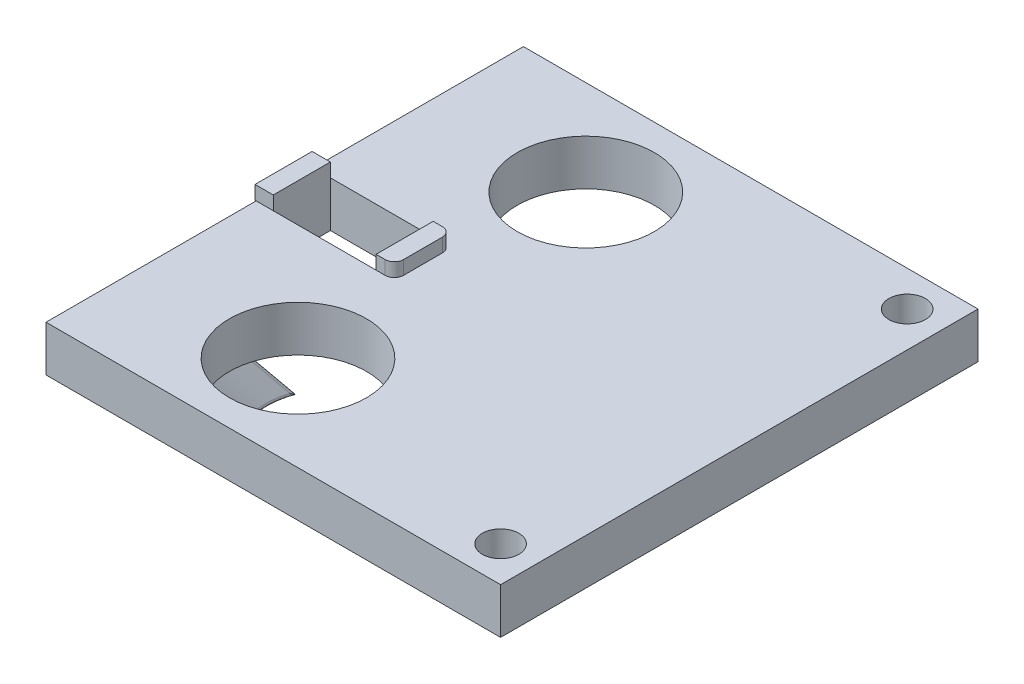
SolidWorks part; units mm, degrees
ref_plane "Front Plane" through (0, 0, 0) normal (0, 0, 1) x (1, 0, 0)
ref_plane "Top Plane" through (0, 0, 0) normal (0, 1, 0) x (1, 0, 0)
ref_plane "Right Plane" through (0, 0, 0) normal (1, 0, 0) x (0, 0, -1)
sketch "Sketch2" plane through (0, 0, 0) normal (0, 1, 0) x (1, 0, 0)
  line L0 (0, 80.9892) -> (0, -86.3988) construction
  line L1 (-50, 52.5) -> (50, 52.5)
  line L2 (-50, 52.5) -> (-50, -52.5)
  line L3 (-50, -52.5) -> (50, -52.5)
  line L4 (50, 52.5) -> (50, -52.5)
  line L5 (-89.0263, 0) -> (108.6553, 0) construction
  dimension "D1" = 100
  dimension "D2" = 105
extrude "Boss-Extrude1" add sketch "Sketch2" along normal blind 10
sketch "Sketch5" plane through (0, 0, 0) normal (0, -1, 0) x (1, 0, 0)
  line L0 (120.2435, 0) -> (-132.425, 0) construction
  line L1 (0, 87.6866) -> (0, -77.6809) construction
  line L2 (-50, -52.5) -> (-50, 52.5) construction
  line L4 (-50, 52.5) -> (50, 52.5) construction
  circle A0 centre (-40, 0) radius 40 construction
  circle A1 centre (-15.3474, 31.5) radius 15
  circle A2 centre (0, 0) radius 15 construction
  circle A4 centre (-40, 0) radius 5
  dimension "D1" = 30
  dimension "D2" = 6
  dimension "D3" = 30
  dimension "D4" = 10
  dimension "D6" = 80
  dimension "D5" = 10
extrude "Cut-Extrude1" cut sketch "Sketch5" against normal up to next
mirror "Mirror1" about plane through (0, 0, 0) normal (0, 0, 1) of "Cut-Extrude1"
sketch "Sketch6" plane through (0, 0, 0) normal (0, -1, 0) x (1, 0, 0)
  line L0 (-56.8508, 0) -> (61.7627, 0) construction
  line L1 (-46, 6.25) -> (-23.5, 6.25)
  line L2 (-46, 6.25) -> (-46, -6.25)
  line L3 (-46, -6.25) -> (-23.5, -6.25)
  line L4 (-23.5, 6.25) -> (-23.5, -6.25)
  circle A0 centre (-40, 0) radius 5 construction
  circle A1 centre (-40, 0) radius 5 construction
  dimension "D1" = 22.5
  dimension "D2" = 12.5
  dimension "D3" = 6
extrude "Cut-Extrude2" cut sketch "Sketch6" against normal up to next
sketch "Sketch7" plane through (0, 0, 0) normal (0, -1, 0) x (1, 0, 0)
  circle A0 centre (-15.3474, 31.5) radius 15 construction
  arc A1 (-6.3521, 43.5035) -> (-28.6119, 24.4962) centre (-15.3474, 31.5) ccw
  arc A2 (-28.6119, 24.4962) -> (-6.3521, 43.5035) centre (-18.5879, 35.295) cw
ref_axis "Axis1" through (-18.5879, 0, 35.295) along (0.6494, 0, -0.7605)
ref_plane "Plane3" through (0.3615, 0, 0.3491) normal (0.7193, 0, 0.6947) x (0, -1, 0)
ref_plane "Plane4" through (7.9146, 0, 7.643) normal (0.7193, 0, 0.6947) x (0, -1, 0)
sketch "Sketch11" plane through (7.9146, 0, 7.643) normal (0.7193, 0, 0.6947) x (0, -1, 0)
  line L0 (0, -49.6877) -> (6.7938, -43.1052)
sweep "Sweep1" add profiles "Sketch7" path "Sketch11"
fillet "Fillet2" radius 0.5 3 edges at (-26.3256, -3.3969, 22.1287) (-4.0658, -3.3969, 41.136) (-20.5152, -6.7938, 38.1721)
sketch "Sketch12" plane through (0, 10, 0) normal (0, 1, 0) x (1, 0, 0)
  line L0 (50, 52.5) -> (-50, 52.5) construction
  line L1 (50, -52.5) -> (50, 52.5) construction
  circle A0 centre (42, 44.5) radius 4
  dimension "D1" = 8
  dimension "D2" = 4
  dimension "D3" = 4
extrude "Cut-Extrude3" cut sketch "Sketch12" against normal up to next
mirror "Mirror2" about plane through (0, 0, 0) normal (0, 0, 1) of "Cut-Extrude3"
sketch "Sketch13" plane through (0, 10, 0) normal (0, 1, 0) x (1, 0, 0)
  line L0 (-46, 6.25) -> (-23.5, 6.25) construction
  line L1 (-50, 6.25) -> (-46, 6.25)
  line L2 (-50, 6.25) -> (-50, -6.25)
  line L3 (-50, -6.25) -> (-46, -6.25)
  line L4 (-46, 6.25) -> (-46, -6.25)
  line L5 (-23.5, 6.25) -> (-19.5, 6.25)
  line L6 (-23.5, 6.25) -> (-23.5, -6.25)
  line L7 (-23.5, -6.25) -> (-19.5, -6.25)
  line L8 (-19.5, 6.25) -> (-19.5, -6.25)
  line L9 (-23.5, -6.25) -> (-46, -6.25) construction
  line L10 (-50, 52.5) -> (-50, -52.5) construction
  line L11 (-46, -6.25) -> (-46, 6.25) construction
  line L12 (-23.5, 6.25) -> (-23.5, -6.25) construction
  dimension "D1" = 4
  dimension "D2" = 4
extrude "Boss-Extrude2" add sketch "Sketch13" along normal blind 3
fillet "Fillet3" radius 2 2 edges at (-19.5, 11.5, -6.25) (-19.5, 11.5, 6.25)
sketch "Sketch14" plane through (0, 10, 0) normal (0, 1, 0) x (1, 0, 0)
  line L0 (50, -52.5) -> (50, 52.5) construction
  line L1 (-49.75, 52.25) -> (49.75, 52.25)
  line L2 (-49.75, 52.25) -> (-49.75, -52.25)
  line L3 (-49.75, -52.25) -> (49.75, -52.25)
  line L4 (49.75, 52.25) -> (49.75, -52.25)
  line L5 (-50, 52.5) -> (-50, 6.25) construction
  line L6 (50, 52.5) -> (-50, 52.5) construction
  line L7 (-50, -52.5) -> (50, -52.5) construction
  line L9 (-83.1777, 63.1049) -> (71.2711, 63.1049)
  line L10 (-83.1777, 63.1049) -> (-83.1777, -59.9)
  line L11 (-83.1777, -59.9) -> (71.2711, -59.9)
  line L12 (71.2711, 63.1049) -> (71.2711, -59.9)
  dimension "D1" = 0.25
  dimension "D2" = 0.25
  dimension "D3" = 0.25
  dimension "D4" = 0.25
extrude "Cut-Extrude6" cut sketch "Sketch14" against normal up to next
